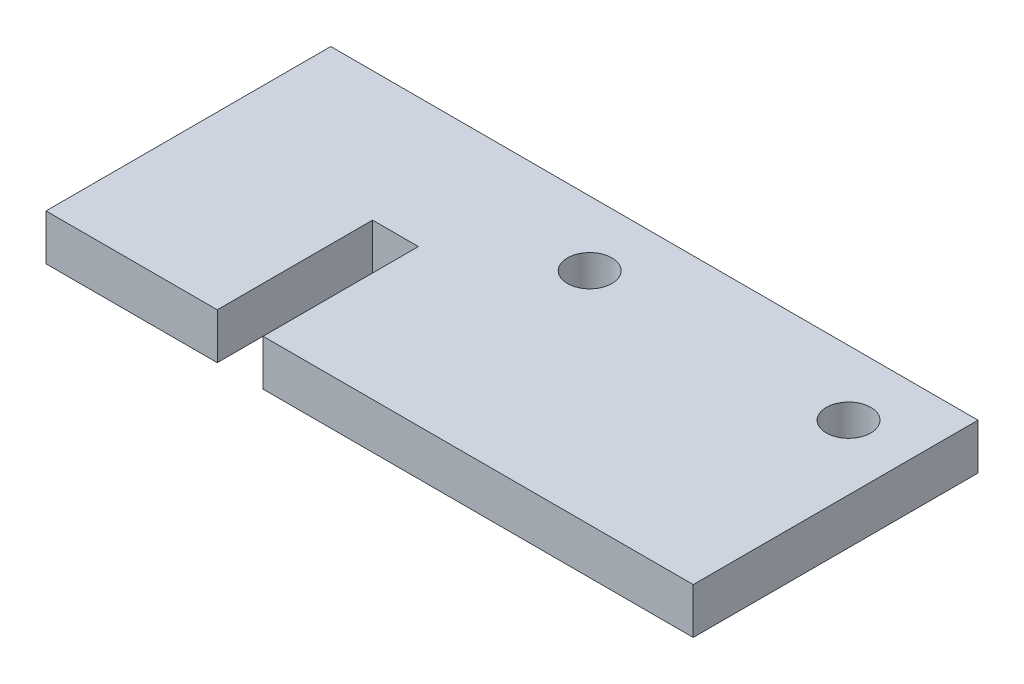
SolidWorks part; units mm, degrees
ref_plane "Front Plane" through (0, 0, 0) normal (0, 0, 1) x (1, 0, 0)
ref_plane "Top Plane" through (0, 0, 0) normal (0, 1, 0) x (1, 0, 0)
ref_plane "Right Plane" through (0, 0, 0) normal (1, 0, 0) x (0, 0, -1)
sketch "Sketch2" plane through (0, 0, 0) normal (0, 1, 0) x (1, 0, 0)
  line L1 (0, 0) -> (63.5, 0)
  line L2 (0, 0) -> (0, 27.94)
  line L3 (0, 27.94) -> (63.5, 27.94)
  line L4 (63.5, 0) -> (63.5, 27.94)
  dimension "D1" = 63.5
  dimension "D2" = 27.94
extrude "Boss-Extrude1" add sketch "Sketch2" along normal blind 4.4958
sketch "Sketch3" plane through (0, 0, 0) normal (0, -1, 0) x (1, 0, 0)
  line L0 (0, 0) -> (63.5, 0) construction
  line L1 (16.8021, 0) -> (21.2979, 0)
  line L2 (16.8021, 0) -> (16.8021, -15.24)
  line L3 (16.8021, -15.24) -> (21.2979, -15.24)
  line L4 (21.2979, 0) -> (21.2979, -15.24)
  line L5 (0, -27.94) -> (0, 0) construction
  dimension "D1" = 15.24
  dimension "D2" = 16.8021
  dimension "D3" = 4.4958
extrude "Cut-Extrude1" cut sketch "Sketch3" against normal through all
sketch "Sketch4" plane through (0, 0, 0) normal (0, -1, 0) x (1, 0, 0)
  line L0 (63.5, 0) -> (63.5, -27.94) construction
  line L1 (63.5, -27.94) -> (0, -27.94) construction
  point P0 (57.15, -21.59)
  point P1 (31.75, -21.59)
  dimension "D1" = 6.35
  dimension "D2" = 6.35
  dimension "D3" = 0
  dimension "D4" = 25.4
hole_wizard "11/64 (0.17188) Diameter Hole1" positions "Sketch5" profile "Sketch6" hole size "11/64" standard "ANSI Inch" end condition through all
sketch "Sketch5" plane through (0, 0, 0) normal (0, -1, 0) x (-1, 0, 0)
  point P0 (-31.75, 21.59)
  point P3 (-57.15, 21.59)
sketch "Sketch6" plane through (31.75, 0, -21.59) normal (1, 0, 0) x (0, 0, -1)
  line L0 (0, 0) -> (0, 4.4958)
  line L1 (0, 4.4958) -> (2.1829, 4.4958)
  line L2 (2.1829, 4.4958) -> (2.1829, 0)
  line L5 (2.1829, 0) -> (0, 0)
  line L11 (0, -6.35) -> (0, 107.95) construction
  dimension "Thru Hole Dia." = 4.3658
  dimension "Thru Hole Depth" = 4.4958
equation "\"support_thickness\"= 0.177"
equation "\"support_height\"= 1.1"
equation "\"support_width\"=1.5"
equation "\"D1@Sketch2\"=\"support_width\"+1"
equation "\"D2@Sketch2\"=\"support_height\""
equation "\"D1@Boss-Extrude1\"=\"support_thickness\""
equation "\"D1@Sketch3\"=\"support_height\"-0.5"
equation "\"D2@Sketch3\"=(\"support_width\"-\"support_thickness\")/2"
equation "\"D3@Sketch3\"=\"support_thickness\""
